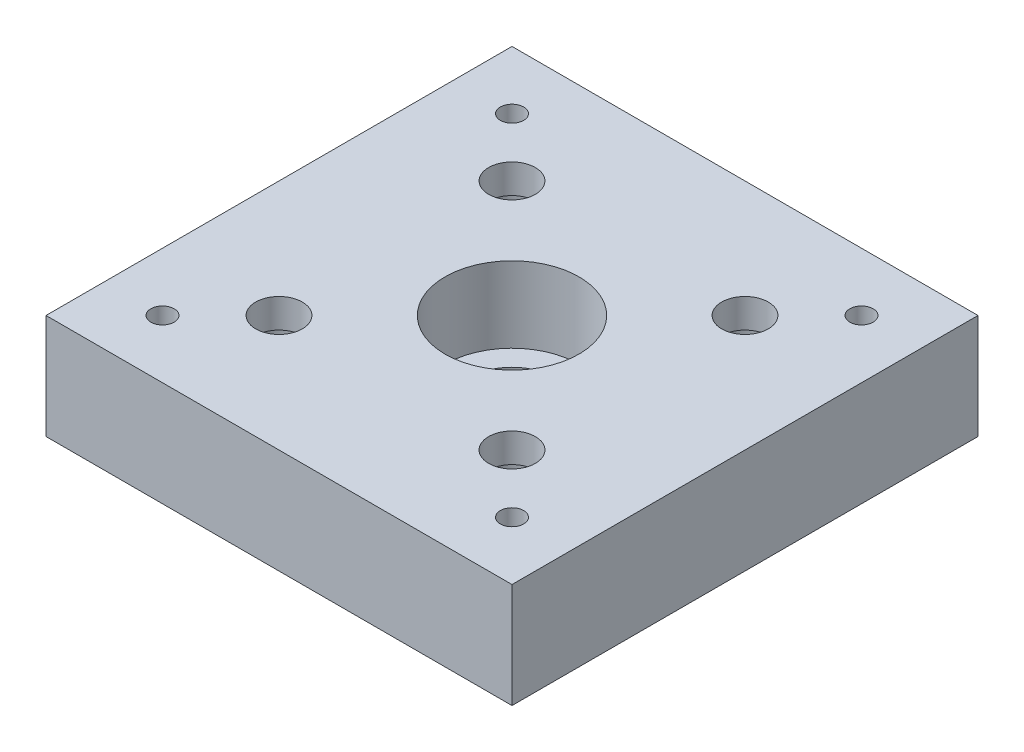
SolidWorks part; units mm, degrees
ref_plane "前视基准面" through (0, 0, 0) normal (0, 0, 1) x (1, 0, 0)
ref_plane "上视基准面" through (0, 0, 0) normal (0, 1, 0) x (1, 0, 0)
ref_plane "右视基准面" through (0, 0, 0) normal (1, 0, 0) x (0, 0, -1)
other "Configuration Table"
sketch "草图1" plane through (0, 0, 0) normal (0, 1, 0) x (1, 0, 0)
  line L1 (-5, -5) -> (5, -5) construction
  line L2 (-5, -5) -> (-5, 5) construction
  line L3 (-5, 5) -> (5, 5) construction
  line L4 (5, -5) -> (5, 5) construction
  line L5 (-5, -5) -> (5, 5) construction
  line L6 (-5, 5) -> (5, -5) construction
  line L7 (-8, -8) -> (8, -8)
  line L8 (-8, -8) -> (-8, 8)
  line L9 (-8, 8) -> (8, 8)
  line L10 (8, -8) -> (8, 8)
  line L11 (-8, -8) -> (8, 8) construction
  line L12 (-8, 8) -> (8, -8) construction
  circle A0 centre (0, 0) radius 1.5
  circle A1 centre (0, 0) radius 2.3
  circle A2 centre (-4, 4) radius 0.8
  circle A3 centre (4, 4) radius 0.8
  circle A4 centre (-4, -4) radius 0.8
  circle A5 centre (4, -4) radius 0.8
  circle A6 centre (-4, 4) radius 1
  circle A7 centre (4, 4) radius 1
  circle A8 centre (4, -4) radius 1
  circle A9 centre (-4, -4) radius 1
  circle A10 centre (-6, 6) radius 0.4
  circle A11 centre (6, 6) radius 0.4
  circle A12 centre (6, -6) radius 0.4
  circle A13 centre (-6, -6) radius 0.4
  point P0 (0, 0)
  point P33 (0, 0)
  point P34 (0, 0)
  point P35 (0, 0)
  dimension "D2" = 4.6
  dimension "D3" = 3
  dimension "D5" = 1.6
  dimension "D6" = 2
  dimension "D8" = 0.8
  dimension "D1" = 10
  dimension "D4" = 1
  dimension "D7" = 16
  dimension "D9" = 2
extrude "凸台-拉伸1" add sketch "草图1" along normal blind 3.6 contours L8 L9 L10 L7 | A0 | A2 | A4 | A5 | A3 | A10 | A11 | A13 | A12
extrude "切除-拉伸1" cut sketch "草图1<3>" against normal offset from surface (2.6 mm away) 1 from surface contours A1 up to face at (0, 0, 0) starting at face at (-6, 3.6, 6.4)
sketch "草图1<3>" plane through (0, 0, 0) normal (0, 1, 0) x (1, 0, 0) same geometry as "草图1"
extrude "切除-拉伸2" cut sketch "草图1<4>" along normal offset from surface (2.6 mm away) 1 contours A8 | A7 | A9 | A6 up to face at (0, 3.6, 2.3)
sketch "草图1<4>" plane through (0, 0, 0) normal (0, 1, 0) x (1, 0, 0) same geometry as "草图1"
